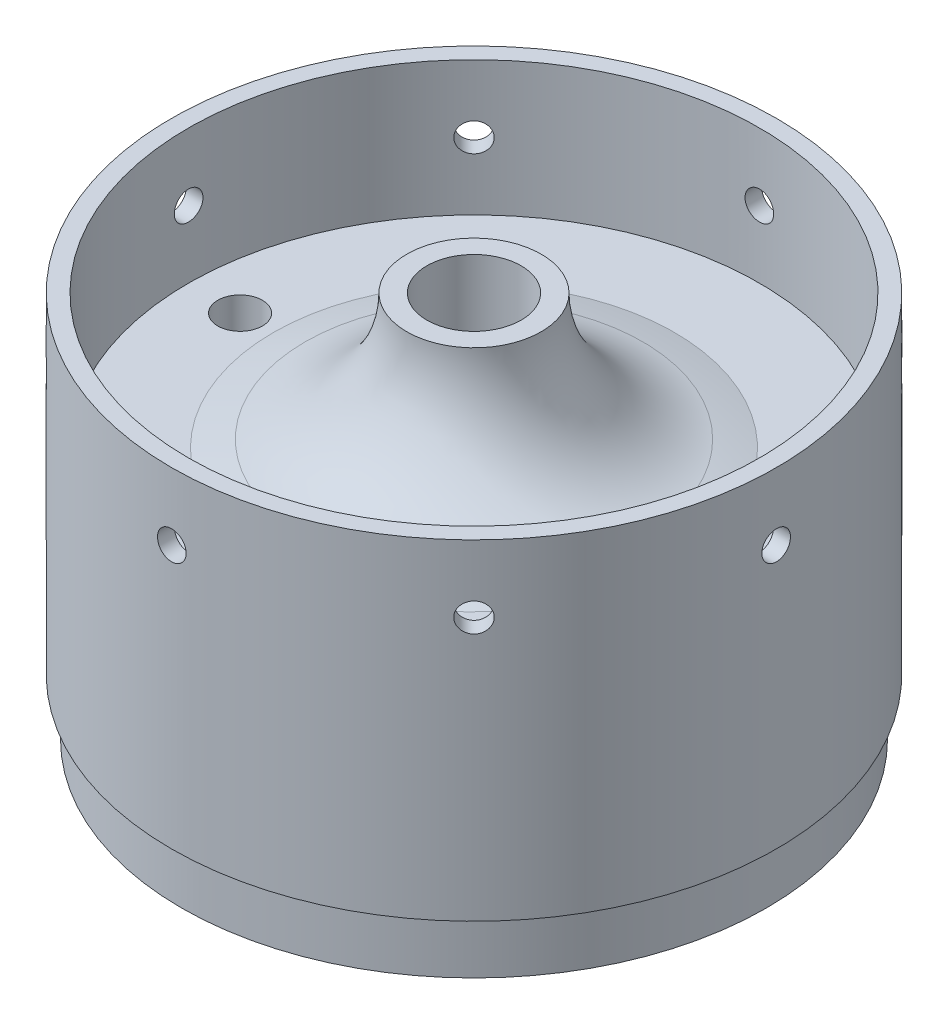
SolidWorks part; units mm, degrees
material "6061-T6 (SS)"
ref_plane "Front Plane" through (0, 0, 0) normal (0, 0, 1) x (1, 0, 0)
ref_plane "Top Plane" through (0, 0, 0) normal (0, 1, 0) x (1, 0, 0)
ref_plane "Right Plane" through (0, 0, 0) normal (1, 0, 0) x (0, 0, -1)
ref_axis "Axis1" through (0, 127.061, 0) along (0, -1, 0)
sketch "Sketch1" plane through (0, 0, 0) normal (0, 0, 1) x (1, 0, 0)
  line L0 (-57.15, 10.6249) -> (-57.15, 73.025)
  line L1 (-55.245, 9.525) -> (-57.15, 10.6249)
  line L2 (0, 127.061) -> (0, -81.9141) construction
  line L3 (-8.9065, 73.025) -> (-12.7, 73.025)
  line L4 (-55.245, 9.525) -> (-55.245, 0)
  line L5 (-55.245, 0) -> (-53.975, 0)
  line L6 (55, 0) -> (-55, 0) construction
  line L7 (-53.975, 73.025) -> (-57.15, 73.025)
  line L8 (-57.15, 10.6249) -> (-55.245, 9.525)
  line L9 (-53.975, 47.625) -> (-37.8832, 47.625)
  line L10 (-8.9065, 73.025) -> (-8.9065, 57.785)
  line L11 (-53.975, 47.625) -> (-53.975, 73.025)
  line L15 (-53.975, 0) -> (-53.975, 9.525)
  line L16 (-53.975, 9.525) -> (-51.7673, 22.0456)
  arc A0 (-51.7673, 22.0456) -> (-37.8832, 40.3817) centre (-32.7173, 22.0456) cw
  arc A1 (-37.8832, 40.3817) -> (-22.9779, 43.7136) centre (0, -94.0837) cw
  arc A2 (-31.8881, 49.0933) -> (-12.7, 73.025) centre (-37.2181, 73.025) ccw
  arc A3 (-37.8832, 47.625) -> (-31.8881, 49.0933) centre (0, -94.0837) cw
  arc A4 (-8.9065, 57.785) -> (-22.9779, 43.7136) centre (-22.9779, 57.785) cw
  point P14 (-54.61, 0)
  dimension "D5" = 19.05
  dimension "D6" = 139.7
  dimension "D7" = 146.685
  dimension "D8" = 63.5
  dimension "D14" = 15.24
  dimension "D2" = 170
  dimension "D3" = 9.525
  dimension "D4" = 1.27
  dimension "D9" = 25.4
  dimension "D10" = 3.175
  dimension "D11" = 12.7
  dimension "D13" = 8.9065
  dimension "D15" = 3.175
  dimension "D16" = 57.15
  dimension "D17" = 120
revolve "Revolve2" add sketch "Sketch1" angle 360 about axis through (0, 127.061, 0) along (0, -1, 0) region at (-38.0177, 44.7504, 0)
sketch "Sketch2" plane through (0, 0, 0) normal (0, 0, 1) x (1, 0, 0)
  line L0 (0, 127.061) -> (0, -81.9141) construction
  line L1 (0, 87.1374) -> (-97.8719, 87.1374)
  line L2 (0, 87.1374) -> (0, -26.2798)
  line L3 (0, -26.2798) -> (-97.8719, -26.2798)
  line L4 (-97.8719, 87.1374) -> (-97.8719, -26.2798)
revolve "Cut-Revolve1" [suppressed] cut sketch "Sketch2" angle 315 about axis through (0, 127.061, 0) along (0, -1, 0)
ref_plane "Plane1" through (0, 60.325, 0) normal (0, 1, 0) x (1, 0, 0)
ref_axis "Axis2" through (0, 60.325, -88.99) along (0, 0, 1)
hole_wizard "#3 (0.213) Diameter Hole1" positions "3DSketch3" profile "Sketch5" hole size "#3" standard "ANSI Inch"
sketch3d "3DSketch3"
  line L0 (0, 60.325, -88.99) -> (0, 60.325, 88.99) construction
  point P0 (0, 60.325, 57.15)
sketch "Sketch5" plane through (0, 60.325, 57.15) normal (1, 0, 0) x (0, -1, 0)
  line L0 (0, 0) -> (0, 13.3094)
  line L1 (0, 13.3094) -> (2.7051, 11.684)
  line L2 (2.7051, 11.684) -> (2.7051, 0)
  line L5 (2.7051, 0) -> (0, 0)
  line L10 (0, 13.3094) -> (-2.7051, 11.684) construction
  line L11 (0, -6.35) -> (0, 107.95) construction
  dimension "Hole Dia." = 5.4102
  dimension "Hole Depth" = 11.684
  dimension "Drill Angle" = 118
pattern_circular "CirPattern1" count 8 over 360 about axis through (0, 127.061, 0) along (0, -1, 0) of "#3 (0.213) Diameter Hole1"
cosmetic thread "Cosmetic Thread1" parameters "D1"=3.2428, "D2"=6.35
hole_wizard "Q (0.332) Diameter Hole2" positions "Sketch9" profile "Sketch10" hole size "Q" standard "ANSI Inch" end condition through all
sketch "Sketch9" plane through (0, 47.625, 0) normal (0, 1, 0) x (1, 0, 0)
  line L0 (-40.1638, 0) -> (40.1638, 0) construction
  circle A1 centre (0, 0) radius 37.8832 construction
  point P0 (-44.196, 0)
  dimension "D1" = 44.196
sketch "Sketch10" plane through (-44.196, 47.625, 0) normal (1, 0, 0) x (0, 0, 1)
  line L0 (0, 0) -> (0, 47.625)
  line L1 (0, 47.625) -> (4.2164, 47.625)
  line L2 (4.2164, 47.625) -> (4.2164, 0)
  line L5 (4.2164, 0) -> (0, 0)
  line L11 (0, -6.35) -> (0, 107.95) construction
  dimension "Thru Hole Dia." = 8.4328
  dimension "Thru Hole Depth" = 47.625
